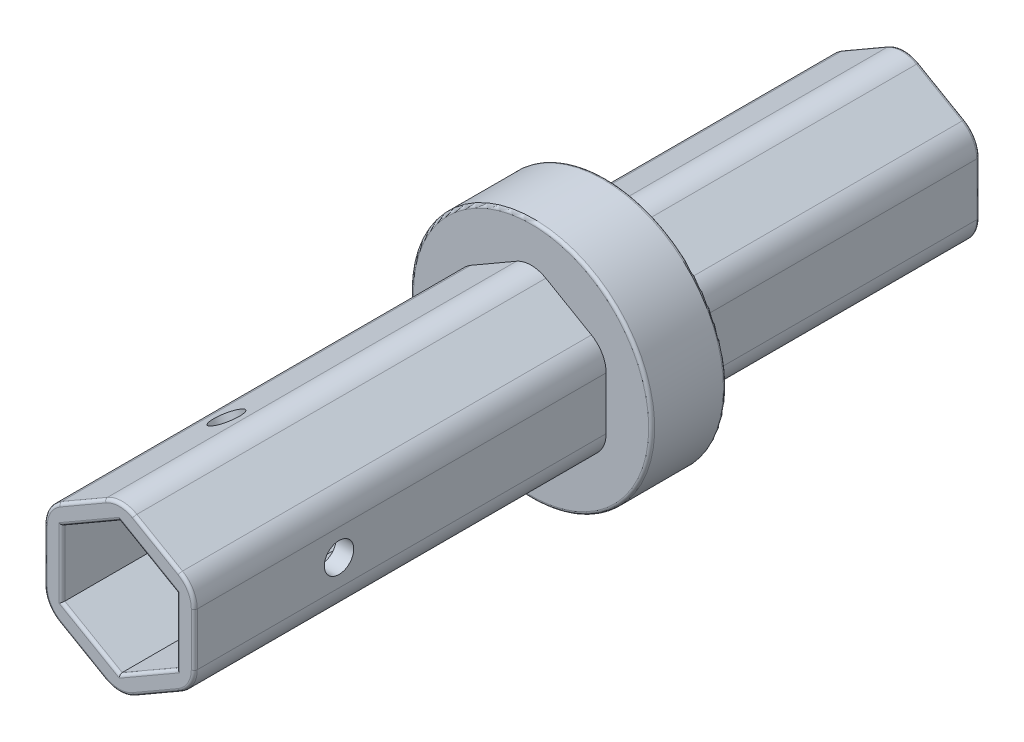
SolidWorks part; units mm, degrees
ref_plane "Front Plane" through (0, 0, 0) normal (0, 0, 1) x (1, 0, 0)
ref_plane "Top Plane" through (0, 0, 0) normal (0, 1, 0) x (1, 0, 0)
ref_plane "Right Plane" through (0, 0, 0) normal (1, 0, 0) x (0, 0, -1)
sketch "Sketch2" plane through (0, 0, 0) normal (0, 1, 0) x (1, 0, 0)
  line L7 (0, 6.35) -> (10.25, 6.35)
  line L8 (10.25, 6.35) -> (10.25, 0)
  line L11 (10.25, 0) -> (0, 0)
  line L14 (0, 6.35) -> (0, 0)
  dimension "D5" = 6.35
  dimension "D1" = 10.25
revolve "Collar" add sketch "Sketch2" angle 360 about L14
sketch "Sketch3" plane through (0, 0, -6.35) normal (0, 0, -1) x (-1, 0, 0)
  line L1 (-6.375, -3.6806) -> (0, -7.3612)
  line L2 (0, -7.3612) -> (6.375, -3.6806)
  line L3 (6.375, -3.6806) -> (6.375, 3.6806)
  line L4 (6.375, 3.6806) -> (0, 7.3612)
  line L5 (0, 7.3612) -> (-6.375, 3.6806)
  line L6 (-6.375, 3.6806) -> (-6.375, -3.6806)
  circle A0 centre (0, 0) radius 6.375 construction
  point P10 (0, 0)
  dimension "D1" = 12.75
extrude "BottomShaft" add sketch "Sketch3" along normal blind 25.4
sketch "Sketch4" plane through (0, 0, 0) normal (0, 0, 1) x (1, 0, 0)
  line L1 (0, -7.3612) -> (6.375, -3.6806)
  line L2 (6.375, -3.6806) -> (6.375, 3.6806)
  line L3 (6.375, 3.6806) -> (0, 7.3612)
  line L4 (0, 7.3612) -> (-6.375, 3.6806)
  line L5 (-6.375, 3.6806) -> (-6.375, -3.6806)
  line L6 (-6.375, -3.6806) -> (0, -7.3612)
  circle A0 centre (0, 0) radius 6.375 construction
  dimension "D1" = 12.75
extrude "TopShaft" add sketch "Sketch4" along normal blind 35
sketch "Sketch5" plane through (0, 0, 35) normal (0, 0, 1) x (1, 0, 0)
  line L12 (-4.875, -2.8146) -> (0, -5.6292)
  line L13 (0, -5.6292) -> (4.875, -2.8146)
  line L14 (4.875, -2.8146) -> (4.875, 2.8146)
  line L15 (4.875, 2.8146) -> (0, 5.6292)
  line L16 (0, 5.6292) -> (-4.875, 2.8146)
  line L17 (-4.875, 2.8146) -> (-4.875, -2.8146)
  line L18 (-4.875, -2.8146) -> (0, -5.6292)
  line L19 (0, -5.6292) -> (4.875, -2.8146)
  line L20 (4.875, -2.8146) -> (4.875, 2.8146)
  line L21 (4.875, 2.8146) -> (0, 5.6292)
  line L22 (0, 5.6292) -> (-4.875, 2.8146)
  line L23 (-4.875, 2.8146) -> (-4.875, -2.8146)
  dimension "D1" = 1.5
extrude "Cut-Extrude1" cut sketch "Sketch5" against normal through all contours L19 L20 L21 L22 L23 L18
sketch "MountHoleLoc" plane through (-3.1875, 5.5209, 0) normal (-0.5, 0.866, 0) x (0.866, 0.5, 0)
  line L0 (0, -8.5359) -> (0, -5.3313) construction
  line L1 (-3.6806, -35) -> (-3.6806, 0) construction
  line L2 (3.6806, -35) -> (3.6806, 0) construction
  line L3 (3.6806, 0) -> (-3.6806, 0) construction
  point P0 (0, -22.7)
  dimension "D1" = 22.7
hole_wizard "MountHole" positions "3DSketch1" profile "Sketch8" hole size "Ø2.5" standard "ANSI Metric" end condition up to next
sketch3d "3DSketch1"
  point P0 (-3.1875, 5.5209, 22.7)
sketch "Sketch8" plane through (-3.1875, 5.5209, 22.7) normal (0, 0, 1) x (-0.866, -0.5, 0)
  line L0 (0, 0) -> (0, 12.75)
  line L1 (0, 12.75) -> (1.25, 12.75)
  line L2 (1.25, 12.75) -> (1.25, 0)
  line L5 (1.25, 0) -> (0, 0)
  line L11 (0, -6.35) -> (0, 107.95) construction
  dimension "Thru Hole Dia." = 2.5
  dimension "Thru Hole Depth" = 12.75
ref_axis "Axis1" through (0, 0, -6.35) along (0, 0, -1)
pattern_circular "MountHoleS" count 3 over 360 about axis through (0, 0, -6.35) along (0, 0, -1) of "MountHole"
fillet "Fillet1" radius 0.254 26 edges at (-10.25, 0, 0) (-10.25, 0, -6.35) (3.1875, 5.5209, -31.75) (-3.1875, 5.5209, -31.75) (-6.375, 0, -31.75) (-3.1875, -5.5209, -31.75) (3.1875, -5.5209, -31.75) (6.375, 0, -31.75) (-6.375, 0, 35) (-3.1875, 5.5209, 35) (3.1875, 5.5209, 35) (6.375, 0, 35) (3.1875, -5.5209, 35) (-3.1875, -5.5209, 35) (-4.875, 0, -31.75) (-2.4375, 4.2219, -31.75) (2.4375, 4.2219, -31.75) (4.875, 0, -31.75) (2.4375, -4.2219, -31.75) (-2.4375, -4.2219, -31.75) (2.4375, -4.2219, 35) (4.875, 0, 35) (2.4375, 4.2219, 35) (-2.4375, 4.2219, 35) (-4.875, 0, 35) (-2.4375, -4.2219, 35)
fillet "Fillet2" radius 2.5 24 edges at (-6.3006, 3.6377, 34.9256) (-6.3006, 3.6377, -31.6756) (-6.3006, -3.6377, -31.6756) (-6.3006, -3.6377, 34.9256) (0, -7.2753, 34.9256) (0, -7.2753, -31.6756) (6.3006, -3.6377, 34.9256) (6.3006, -3.6377, -31.6756) (6.3006, 3.6377, -31.6756) (6.3006, 3.6377, 34.9256) (0, 7.2753, 34.9256) (0, 7.2753, -31.6756) (0, 7.3612, -18.923) (0, 7.3612, 17.373) (6.375, 3.6806, 17.373) (6.375, 3.6806, -18.923) (6.375, -3.6806, -18.923) (6.375, -3.6806, 17.373) (0, -7.3612, -18.923) (0, -7.3612, 17.373) (-6.375, -3.6806, 17.373) (-6.375, -3.6806, -18.923) (-6.375, 3.6806, -18.923) (-6.375, 3.6806, 17.373)
equation "\"D1@Sketch3\"=\"HEXSHAFT_D\""
equation "\"D1@Sketch4\"=\"HEXSHAFT_D\""
equation "\"D1@Fillet2\"=\"HEXSHAFT_FILLET\""
equation "\"CB_W\" = 5"
equation "\"CW_DEPTH\" = 1"
equation "\"PIN_SPACING\" = 2.54"
equation "\"PIN_D\" = 1"
equation "\"PCB_THICK\" = 1.5"
equation "\"TAP_HOLE\" = 2.5"
equation "\"SCREW_HOLE\" = 3"
equation "\"SLIPRING_D\" = 12.4"
equation "\"SLIPRING_MOUNTOD\" = 15"
equation "\"SLIPRING_MOUNTTHICK\" = 8"
equation "\"SLIPRING_MOUNT_LEGH\" = 12"
equation "\"PITCH_D\"= 44.45"
equation "\"HEX_D\"= 12.7"
equation "\"BODY_Y\"= 70"
equation "\"BODY_X\"= 60"
equation "\"BODY_Z\"= 120"
equation "\"BODY_THICK\"= 3"
equation "\"BODY_TOPTHICK\"= 4"
equation "\"STAND_R\" = 3"
equation "\"STAND_ZOFF\" = 10"
equation "\"STAND_XOFF\" = 5"
equation "\"MOTOR_ZOFF\" = 25"
equation "\"MOTOR_MOUNTANGLE\" = 120"
equation "\"MOTOR_D\"= 28"
equation "\"MOTOR_H\"= 19"
equation "\"MOTOR_HOLEDIST\"= 35"
equation "\"MOTOR_SHAFTOFF\" = 8"
equation "\"DRVR_Y\" = 31"
equation "\"DRVR_Z\" = 27"
equation "\"DRVR_YOFF\" = 15"
equation "\"DRVR_ARDOFF\" = 10"
equation "\"BEARING_OD\" = 28.575"
equation "\"BEARING_ID\" = 12.7"
equation "\"BEARING_THICK\" = 7.925"
equation "\"BEARING_FLANGE_D\" = 31.242"
equation "\"BEARING_FLANGETHICK\" = 1.575"
equation "\"BMOUNT_X\" = 30"
equation "\"BMOUNT_HEXID\" = 15"
equation "\"BMOUNT_HEXTHICK\" = 2"
equation "\"BMOUNT_HEXH\" = 35"
equation "\"BMOUNT_HOLEX\" = 4*\"PIN_SPACING\""
equation "\"BMOUNT_HOLEZ\" = 4*\"PIN_SPACING\""
equation "\"BMOUNT_SCREWH\" = 5"
equation "\"MBOARD_MHOLEX\" = 10*\"PIN_SPACING\""
equation "\"MBOARD_MHOLEXOFF\" = 2*\"PIN_SPACING\""
equation "\"MBOARD_MHOLEZ\" = 9*\"PIN_SPACING\""
equation "\"MBOARD_POGOSPACING\" = 1*\"PIN_SPACING\""
equation "\"MBOARD_POGOX\" = 7*\"PIN_SPACING\""
equation "\"MBOARD_POGOXOFF\" = 1*\"PIN_SPACING\""
equation "\"MBOARD_POGOZ\" = 7*\"PIN_SPACING\""
equation "\"MBOARD_W\" = 28*\"PIN_SPACING\""
equation "\"SHAFT_BASEID\" = 12.7"
equation "\"SHAFT_BASEOD\" = \"SHAFT_BASEID\" + 2*3"
equation "\"SHAFT_BASEHOLEH\" = 10"
equation "\"SHAFT_MOUNTOD\" = \"BMOUNT_HEXID\""
equation "\"SHAFT_MOUNTTHICK\" = 1.5"
equation "\"SHAFT_MOUNTH\" = \"BMOUNT_HEXH\" "
equation "\"SHAFT_D\" = 18"
equation "\"DRIVESHAFT_COLLARH\" = 20"
equation "\"DRIVESHAFT_LENGTH\" = 58"
equation "\"DRIVESHAFT_MOUNTD\" = 7.6"
equation "\"DRIVESHAFT_HOLED\" = 4.8"
equation "\"DRIVESHAFT_HOLEW\" = 2.9"
equation "\"HEXSHAFT_D\" = 12.75"
equation "\"HEXSHAFT_FILLET\" = 2.5"
equation "\"COLLAR_OD\" = 20.5"
equation "\"COLLAR_THICK\" = 6.35"
equation "\"D1@Sketch2\"=\"COLLAR_OD\"/2"
equation "\"D5@Sketch2\"=\"COLLAR_THICK\""
equation "\"DRIVENSHAFT_THICK\" = 1.5"
equation "\"D1@Sketch5\"=\"DRIVENSHAFT_THICK\""
equation "\"DRIVENSHAFT_TOPLENGTH\" = 35"
equation "\"DRIVENSHAFT_BOTTOMLENGTH\" = 25.4"
equation "\"D1@TopShaft\"=\"DRIVENSHAFT_TOPLENGTH\""
equation "\"D1@BottomShaft\"=\"DRIVENSHAFT_BOTTOMLENGTH\""
equation "\"D1@MountHoleLoc\"=\"DRIVENSHAFT_HOLEH\""
equation "\"DRIVENSHAFT_HOLEH\" = \"SHAFT_BASEHOLEH\" + 12.7"
equation "\"SHAFT_OD\" = \"BEARING_ID\" + \"TOLERANCE\""
